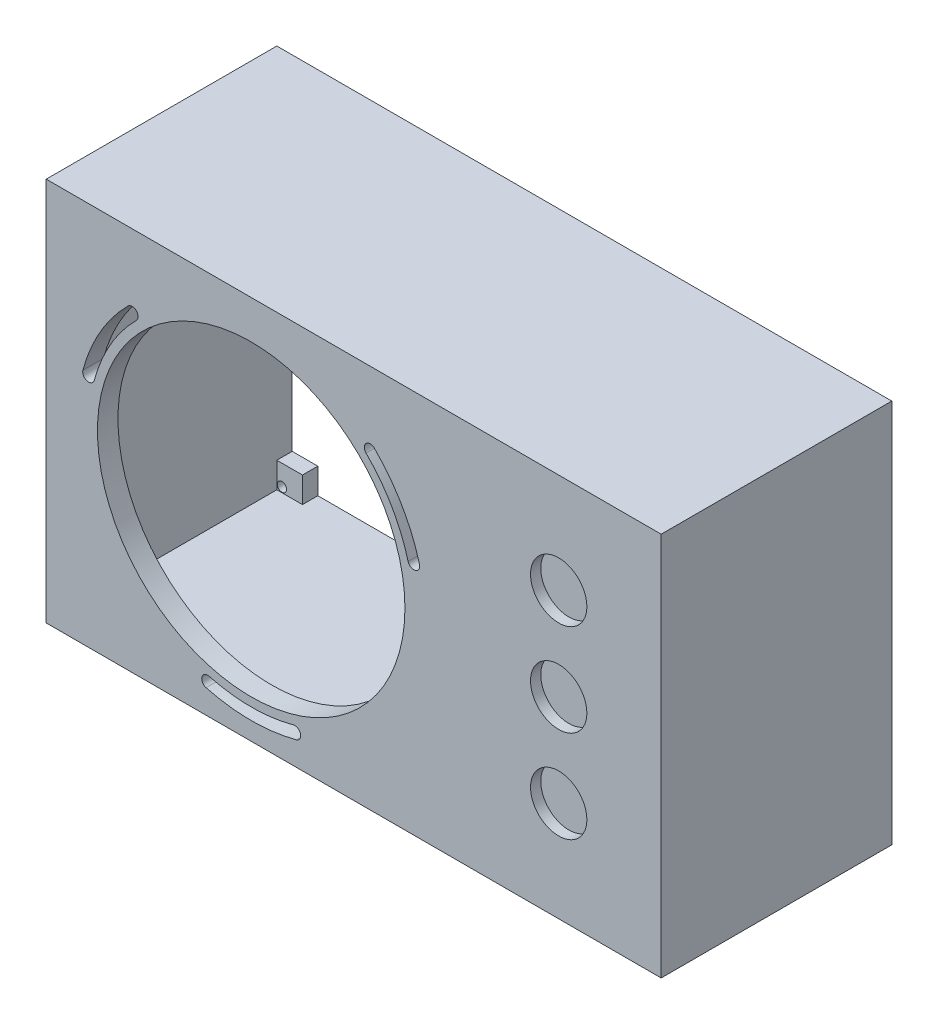
SolidWorks part; units mm, degrees
ref_plane "前视基准面" through (0, 0, 0) normal (0, 0, 1) x (1, 0, 0)
ref_plane "上视基准面" through (0, 0, 0) normal (0, 1, 0) x (1, 0, 0)
ref_plane "右视基准面" through (0, 0, 0) normal (1, 0, 0) x (0, 0, -1)
other "Configuration Table"
sketch "草图1" plane through (0, 0, 0) normal (0, 0, 1) x (1, 0, 0)
  line L1 (-60, -37.5) -> (60, -37.5)
  line L2 (-60, -37.5) -> (-60, 37.5)
  line L3 (-60, 37.5) -> (60, 37.5)
  line L4 (60, -37.5) -> (60, 37.5)
  line L5 (-60, -37.5) -> (60, 37.5) construction
  line L6 (-60, 37.5) -> (60, -37.5) construction
  line L7 (-57, -34.5) -> (57, -34.5)
  line L8 (-57, -34.5) -> (-57, 34.5)
  line L9 (-57, 34.5) -> (57, 34.5)
  line L10 (57, -34.5) -> (57, 34.5)
  line L11 (-57, -34.5) -> (57, 34.5) construction
  line L12 (-57, 34.5) -> (57, -34.5) construction
  point P0 (0, 0)
  point P6 (0, 0)
  dimension "D1" = 120
  dimension "D2" = 75
  dimension "D3" = 3
  dimension "D4" = 3
extrude "凸台-拉伸1" add sketch "草图1" along normal blind 45
sketch "草图2" plane through (0, 0, 45) normal (0, 0, 1) x (1, 0, 0)
  line L0 (-60, -37.5) -> (60, -37.5) construction
  line L1 (-60, 37.5) -> (20, 37.5)
  line L2 (-60, 37.5) -> (-60, -37.5)
  line L3 (-60, -37.5) -> (20, -37.5)
  line L4 (20, 37.5) -> (20, -37.5)
  line L5 (-20, 37.5) -> (-20, -37.5) construction
  line L6 (60, -37.5) -> (60, 37.5) construction
  line L7 (20, 37.5) -> (60, 37.5)
  line L8 (20, 37.5) -> (20, -37.5)
  line L9 (20, -37.5) -> (60, -37.5)
  line L10 (60, 37.5) -> (60, -37.5)
  line L11 (-43.2285, 23.2285) -> (-20, 0) construction
  line L12 (-20, 0) -> (-51.7307, 8.5022) construction
  line L13 (-28.5022, -31.7307) -> (-20, 0) construction
  line L14 (-20, 0) -> (-11.4978, -31.7307) construction
  line L15 (11.7307, 8.5022) -> (-20, 0) construction
  line L16 (3.2285, 23.2285) -> (-20, 0) construction
  line L17 (-48.4489, 16.425) -> (-20, 0) construction
  line L18 (-20, 0) -> (5.9808, 15) construction
  circle A0 centre (-20, 0) radius 30
  circle A1 centre (-20, 0) radius 34
  circle A2 centre (-43.2285, 23.2285) radius 1.15
  circle A3 centre (-51.7307, 8.5022) radius 1.15
  circle A4 centre (-20, 0) radius 32.85
  circle A5 centre (-28.5022, -31.7307) radius 1.15
  circle A6 centre (-11.4978, -31.7307) radius 1.15
  circle A7 centre (11.7307, 8.5022) radius 1.15
  circle A8 centre (3.2285, 23.2285) radius 1.15
  circle A11 centre (-20, 0) radius 31.7
  line M11 (57, 34.5) -> (57, -34.5)
  line M12 (57, -34.5) -> (-57, -34.5)
  line M14 (-57, 34.5) -> (57, 34.5)
  dimension "D2" = 60
  dimension "D3" = 4
  dimension "D4" = 30
  dimension "D12" = 2.3
  dimension "D1" = 80
  dimension "D5" = 120
  dimension "D6" = 30
  dimension "D7" = 30
  dimension "D8" = 120
  dimension "D9" = 15
  dimension "D10" = 15
  dimension "D11" = 15
extrude "凸台-拉伸2" add sketch "草图2" against normal blind 4 contours L4 M14 M12 M11 | L2 L3 L4 L1 | A0 region at (38.5, 0, 45)
extrude "切除-拉伸1" cut sketch "草图2<4>" against normal through all contours A2 A4 | A4 A2 | A2 A3 A4 | A11 A2 A4 A3 | A3 A4 | A4 A3 | A4 A5 | A4 A5 | A11 A5 A4 A6 | A5 A6 A4 | A4 A6 | A4 A6 | A4 A7 | A4 A7 | A7 A8 A4 | A11 A7 A4 A8 | A4 A8 | A4 A8 region at (8.6928, 16.5658, 45) region at (12.1986, 8.6276, 45) region at (-20, -33.1315, 45) region at (-11.3724, -32.1986, 45) region at (3.571, 23.571, 45) region at (7.6901, 15.9869, 45) region at (11.2557, 8.3749, 45) region at (-28.6276, -32.1986, 45) region at (-11.6251, -31.2557, 45) region at (-20, -31.9738, 45) region at (-48.6928, 16.5658, 45) region at (-43.571, 23.571, 45) region at (2.8808, 22.8808, 45) region at (-52.1986, 8.6276, 45) region at (-28.3749, -31.2557, 45) region at (-42.8808, 22.8808, 45) region at (-47.6901, 15.9869, 45) region at (-51.2557, 8.3749, 45)
sketch "草图2<4>" plane through (0, 0, 45) normal (0, 0, 1) x (1, 0, 0) same geometry as "草图2"
sketch "草图3" plane through (0, 0, 0) normal (0, 0, -1) x (-1, 0, 0)
  line L1 (-60, 37.5) -> (-52, 37.5)
  line L2 (-60, 37.5) -> (-60, 29.5)
  line L3 (-60, 29.5) -> (-52, 29.5)
  line L4 (-52, 37.5) -> (-52, 29.5)
  line L5 (60, 37.5) -> (52, 37.5)
  line L6 (60, 37.5) -> (60, 29.5)
  line L7 (60, 29.5) -> (52, 29.5)
  line L8 (52, 37.5) -> (52, 29.5)
  line L9 (-60, -37.5) -> (-52, -37.5)
  line L10 (-60, -37.5) -> (-60, -29.5)
  line L11 (-60, -29.5) -> (-52, -29.5)
  line L12 (-52, -37.5) -> (-52, -29.5)
  line L13 (60, -37.5) -> (52, -37.5)
  line L14 (60, -37.5) -> (60, -29.5)
  line L15 (60, -29.5) -> (52, -29.5)
  line L16 (52, -37.5) -> (52, -29.5)
  circle A0 centre (-56, 33.5) radius 0.9
  circle A1 centre (-56, -33.5) radius 0.9
  circle A2 centre (56, -33.5) radius 0.9
  circle A3 centre (56, 33.5) radius 0.9
  dimension "D4" = 1.8
  dimension "D1" = 8
  dimension "D2" = 4
  dimension "D3" = 4
  dimension "D5" = 4
  dimension "D6" = 4
extrude "凸台-拉伸3" add sketch "草图3" against normal blind 3 contours L12 L11 L10 L9 | L15 L16 L13 L14 | L3 L4 L1 L2 | L7 L8 L5 L6
extrude "切除-拉伸2" cut sketch "草图3<3>" against normal blind 3 contours A0 | A1 | A2 | A3
sketch "草图3<3>" plane through (0, 0, 0) normal (0, 0, -1) x (-1, 0, 0) same geometry as "草图3"
sketch "草图4" plane through (0, 0, 45) normal (0, 0, 1) x (1, 0, 0)
  circle A4 centre (40, 18) radius 5.5
  circle A5 centre (40, 0) radius 5.5
  circle A6 centre (40, -18) radius 5.5
  point P6 (0, 0)
  dimension "D1" = 11
extrude "切除-拉伸3" cut sketch "草图4" against normal blind 2
